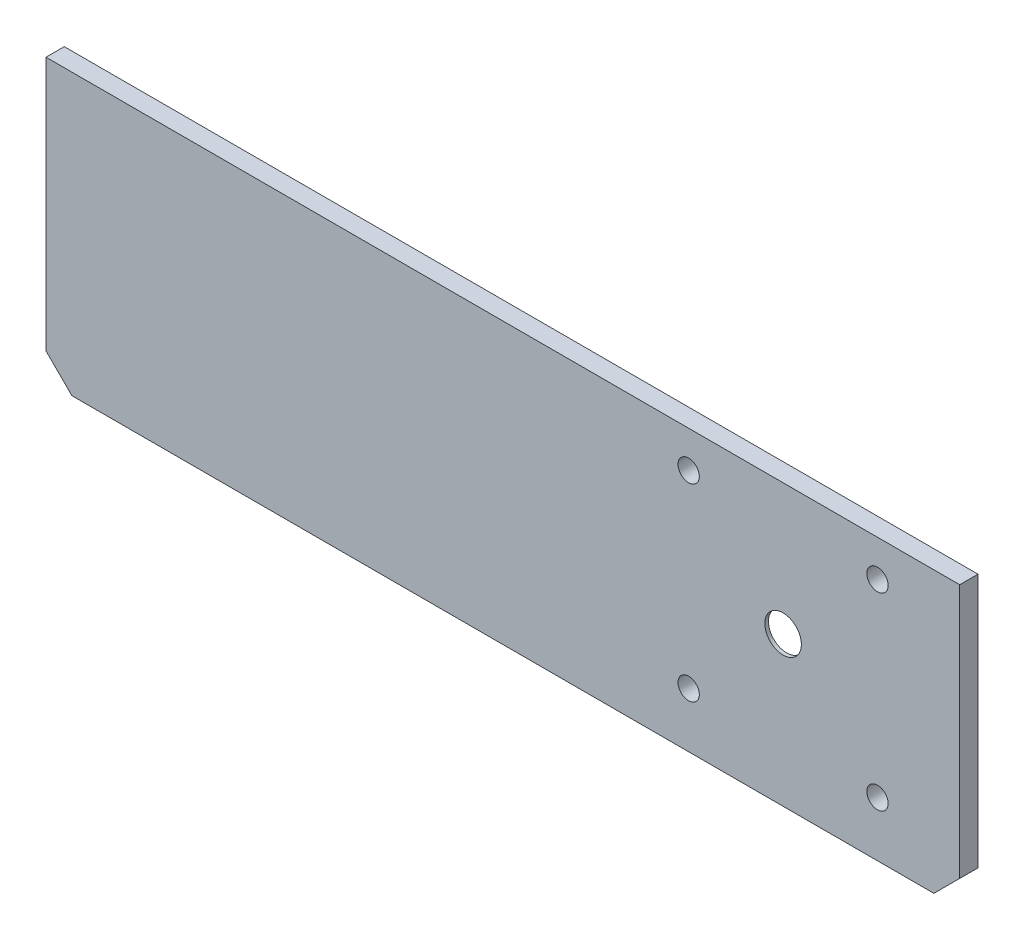
SolidWorks part; units mm, degrees
ref_plane "Front Plane" through (0, 0, 0) normal (0, 0, 1) x (1, 0, 0)
ref_plane "Top Plane" through (0, 0, 0) normal (0, 1, 0) x (1, 0, 0)
ref_plane "Right Plane" through (0, 0, 0) normal (1, 0, 0) x (0, 0, -1)
sketch "Sketch1" plane through (0, 0, 0) normal (0, 0, 1) x (1, 0, 0)
  line L0 (-121, 21.5) -> (29, 21.5)
  line L1 (29, 21.5) -> (29, -20.2574)
  line L2 (29, -20.2574) -> (24.7574, -24.5)
  line L3 (24.7574, -24.5) -> (-116.7574, -24.5)
  line L4 (-116.7574, -24.5) -> (-121, -20.2574)
  line L5 (-121, -20.2574) -> (-121, 21.5)
  line L6 (-14.5858, 21) -> (14.5858, 21) construction
  line L7 (21, 14.5858) -> (21, -14.5858) construction
  line L8 (14.5858, -21) -> (-14.5858, -21) construction
  circle A0 centre (15.5, 15.5) radius 1.75
  circle A1 centre (-15.5, 15.5) radius 1.75
  circle A2 centre (15.5, -15.5) radius 1.75
  circle A3 centre (-15.5, -15.5) radius 1.75
  circle A4 centre (0, 0) radius 3
  dimension "D1" = 3.5
  dimension "D8" = 6
  dimension "D2" = 0.5
  dimension "D3" = 8
  dimension "D4" = 135
  dimension "D5" = 6
  dimension "D6" = 3.5
  dimension "D7" = 150
extrude "Boss-Extrude1" add sketch "Sketch1" along normal blind 3
sketch "Sketch2" plane through (0, 0, 0) normal (0, 0, -1) x (-1, 0, 0)
  circle A2 centre (0, 0) radius 11.45
  circle A3 centre (0, 0) radius 11.45
  dimension "D1" = 0.2
extrude "Cut-Extrude1" cut sketch "Sketch2" against normal blind 2.4
